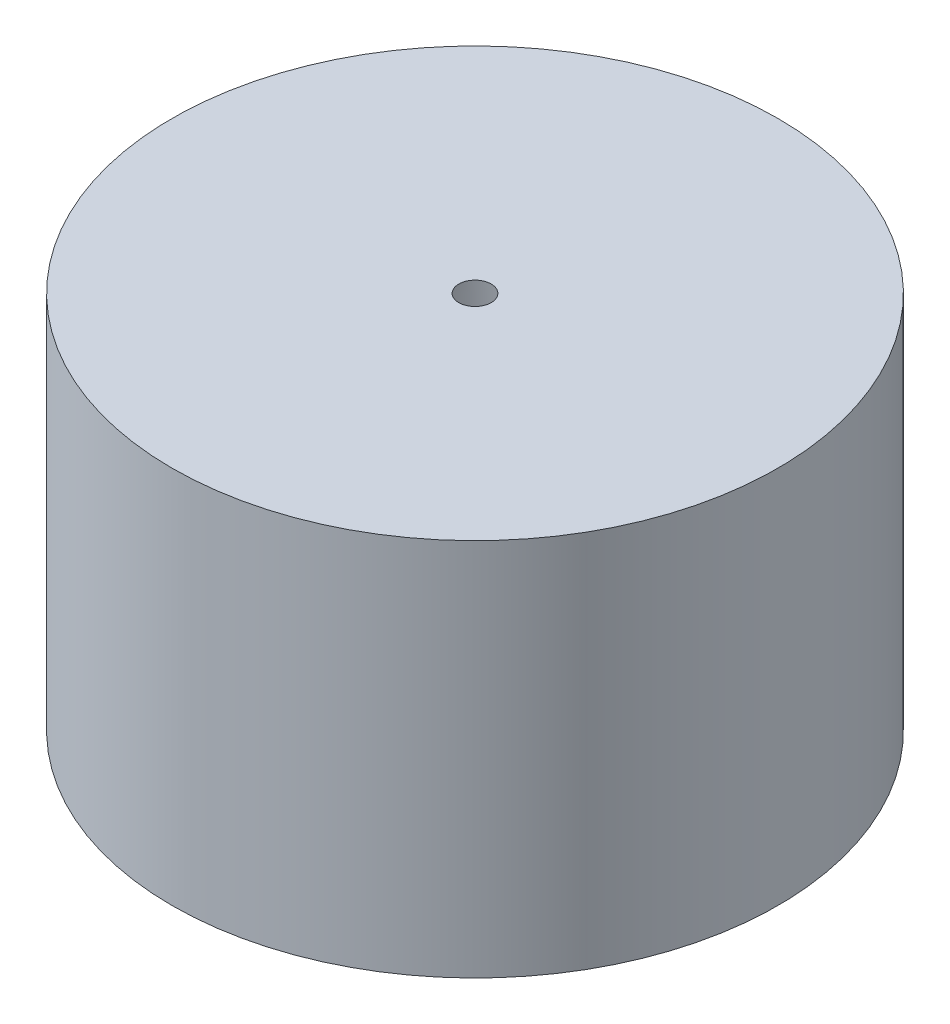
SolidWorks part; units mm, degrees
ref_plane "Спереди" through (0, 0, 0) normal (0, 0, 1) x (1, 0, 0)
ref_plane "Сверху" through (0, 0, 0) normal (0, 1, 0) x (1, 0, 0)
ref_plane "Справа" through (0, 0, 0) normal (1, 0, 0) x (0, 0, -1)
sketch "Эскиз1" plane through (0, 0, 0) normal (0, 0, 1) x (1, 0, 0)
  line L0 (0, 0) -> (0, 60) construction
  line L1 (17, 27) -> (17, 25.8)
  line L17 (12.7862, 32) -> (17, 27)
  line L29 (17, 25.8) -> (30, 25.8)
  line L33 (30, 25.8) -> (30, 23.3)
  line L34 (30, 23.3) -> (28.4, 23.3)
  line L35 (28.4, 23.3) -> (28.4, 15.3)
  line L37 (8, 58.6338) -> (2, 62.0979)
  line L38 (2, 62.0979) -> (37.4277, 62.0979)
  line L40 (28.4, 15.3) -> (37.4277, 15.3)
  line L41 (37.4277, 15.3) -> (37.4277, 62.0979)
  line L42 (8, 58.6338) -> (8.3476, 52.0019)
  line L43 (8.3476, 52.0019) -> (12, 47.0019)
  line L44 (8, 58.6338) -> (8, 51.4355) construction
  line L45 (12, 47.0019) -> (12.7862, 32)
  line L46 (12, 47.0019) -> (12, 37.0019) construction
  dimension "D5" = 16
  dimension "D7" = 5
  dimension "D3" = 5
  dimension "D4" = 3
  dimension "D6" = 60
  dimension "D8" = 4
  dimension "D9" = 3
  dimension "D18" = 34
  dimension "D19" = 1.2
  dimension "D20" = 2.5
  dimension "D21" = 8
  dimension "D22" = 13
  dimension "D23" = 1.6
revolve "Повернуть1" add sketch "Эскиз1" angle 360 about L0 reverse direction yes
